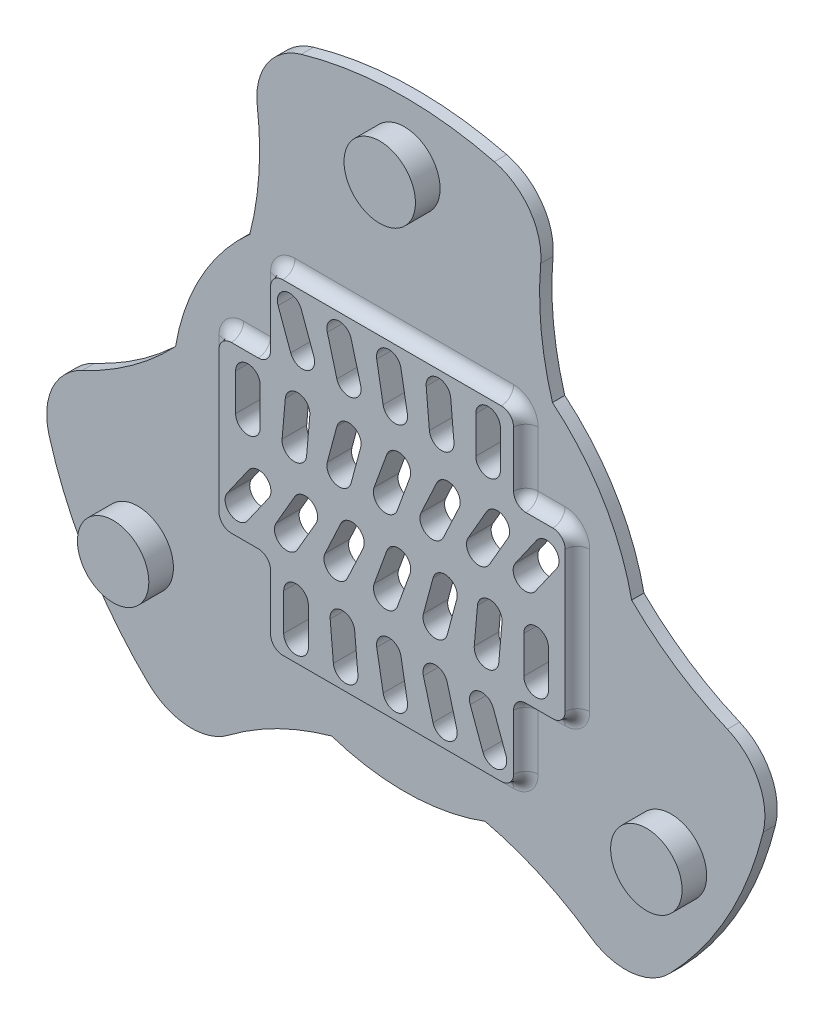
SolidWorks part; units mm, degrees
ref_plane "Спереди" through (0, 0, 0) normal (0, 0, 1) x (1, 0, 0)
ref_plane "Сверху" through (0, 0, 0) normal (0, 1, 0) x (1, 0, 0)
ref_plane "Справа" through (0, 0, 0) normal (1, 0, 0) x (0, 0, -1)
sketch "Sketch1" plane through (0, 0, 0) normal (0, 0, 1) x (1, 0, 0)
  line L0 (3.9, 6.755) -> (7.8, 0) construction
  line L2 (5.85, 10.1325) -> (11.7, 0) construction
  line L4 (7.8, 13.51) -> (15.6, 0) construction
  circle A61 centre (0, 0) radius 20
  circle A131 centre (0, 0) radius 1.25
  circle A484 centre (3.9, 0) radius 1.25
  circle A485 centre (7.8, 0) radius 1.25
  circle A486 centre (11.7, 0) radius 1.25
  circle A487 centre (15.6, 0) radius 1.25
  circle A488 centre (1.95, -3.3775) radius 1.25
  circle A489 centre (3.9, -6.755) radius 1.25
  circle A490 centre (5.85, -10.1325) radius 1.25
  circle A491 centre (7.8, -13.51) radius 1.25
  circle A492 centre (-1.95, -3.3775) radius 1.25
  circle A493 centre (-3.9, -6.755) radius 1.25
  circle A494 centre (-5.85, -10.1325) radius 1.25
  circle A495 centre (-7.8, -13.51) radius 1.25
  circle A496 centre (-3.9, 0) radius 1.25
  circle A497 centre (-7.8, 0) radius 1.25
  circle A498 centre (-11.7, 0) radius 1.25
  circle A499 centre (-15.6, 0) radius 1.25
  circle A500 centre (-1.95, 3.3775) radius 1.25
  circle A501 centre (-3.9, 6.755) radius 1.25
  circle A502 centre (-5.85, 10.1325) radius 1.25
  circle A503 centre (-7.8, 13.51) radius 1.25
  circle A504 centre (1.95, 3.3775) radius 1.25
  circle A505 centre (3.9, 6.755) radius 1.25
  circle A506 centre (5.85, 10.1325) radius 1.25
  circle A507 centre (7.8, 13.51) radius 1.25
  circle A508 centre (5.85, 3.3775) radius 1.25
  circle A509 centre (7.8, 6.755) radius 1.25
  circle A510 centre (9.75, 3.3775) radius 1.25
  circle A511 centre (11.7, 6.755) radius 1.25
  circle A512 centre (9.7491, 10.1341) radius 1.25
  circle A513 centre (13.6509, 3.3759) radius 1.25
  circle A514 centre (5.85, -3.3791) radius 1.25
  circle A515 centre (9.75, -3.3791) radius 1.25
  circle A516 centre (7.8, -6.7566) radius 1.25
  circle A517 centre (11.7, -6.7566) radius 1.25
  circle A518 centre (9.7491, -10.1356) radius 1.25
  circle A519 centre (13.6509, -3.3775) radius 1.25
  circle A520 centre (-0.0013, -6.7573) radius 1.25
  circle A521 centre (1.9487, -10.1348) radius 1.25
  circle A522 centre (-1.9513, -10.1348) radius 1.25
  circle A523 centre (-0.0013, -13.5123) radius 1.25
  circle A524 centre (-3.9032, -13.5123) radius 1.25
  circle A525 centre (3.9005, -13.5123) radius 1.25
  circle A526 centre (-5.8527, -3.3791) radius 1.25
  circle A527 centre (-7.8027, -6.7566) radius 1.25
  circle A528 centre (-9.7527, -3.3791) radius 1.25
  circle A529 centre (-11.7027, -6.7566) radius 1.25
  circle A530 centre (-13.6536, -3.3775) radius 1.25
  circle A531 centre (-9.7518, -10.1356) radius 1.25
  circle A532 centre (-5.8527, 3.3775) radius 1.25
  circle A533 centre (-9.7527, 3.3775) radius 1.25
  circle A534 centre (-7.8027, 6.755) radius 1.25
  circle A535 centre (-11.7027, 6.755) radius 1.25
  circle A536 centre (-9.7518, 10.1341) radius 1.25
  circle A537 centre (-13.6536, 3.3759) radius 1.25
  circle A538 centre (-0.0014, 6.7558) radius 1.25
  circle A539 centre (-1.9514, 10.1333) radius 1.25
  circle A540 centre (1.9486, 10.1333) radius 1.25
  circle A541 centre (-0.0014, 13.5108) radius 1.25
  circle A542 centre (3.9005, 13.5108) radius 1.25
  circle A543 centre (-3.9032, 13.5108) radius 1.25
  circle A544 centre (13.65, -1.1258) radius 2.2517 construction
  circle A545 centre (11.7009, -4.5044) radius 2.2522 construction
  circle A546 centre (9.75, -7.8834) radius 2.2522 construction
  circle A547 centre (7.7987, -11.2591) radius 2.2509 construction
  circle A548 centre (13.65, -1.1258) radius 0.65
  circle A549 centre (11.7009, -4.5044) radius 0.65
  circle A550 centre (9.75, -7.8834) radius 0.65
  circle A551 centre (7.7987, -11.2591) radius 0.65
  circle A552 centre (9.75, -1.1258) radius 0.65
  circle A553 centre (7.8009, -4.5044) radius 0.65
  circle A554 centre (5.85, -7.8834) radius 0.65
  circle A555 centre (3.8987, -11.2591) radius 0.65
  circle A556 centre (5.85, -1.1258) radius 0.65
  circle A557 centre (3.9009, -4.5044) radius 0.65
  circle A558 centre (1.95, -7.8834) radius 0.65
  circle A559 centre (-0.0013, -11.2591) radius 0.65
  circle A560 centre (1.95, -1.1258) radius 0.65
  circle A561 centre (0.0009, -4.5044) radius 0.65
  circle A562 centre (-1.95, -7.8834) radius 0.65
  circle A563 centre (-3.9013, -11.2591) radius 0.65
  circle A564 centre (-1.95, -1.1258) radius 0.65
  circle A565 centre (-3.8991, -4.5044) radius 0.65
  circle A566 centre (-5.85, -7.8834) radius 0.65
  circle A567 centre (-7.8013, -11.2591) radius 0.65
  circle A568 centre (-5.85, -1.1258) radius 0.65
  circle A569 centre (-7.7991, -4.5044) radius 0.65
  circle A570 centre (-9.75, -7.8834) radius 0.65
  circle A572 centre (-9.75, -1.1258) radius 0.65
  circle A573 centre (-11.6991, -4.5044) radius 0.65
  circle A576 centre (-13.65, -1.1258) radius 0.65
  circle A587 centre (0, 2.2517) radius 2.2517 construction
  circle A588 centre (0, 2.2517) radius 0.65
  circle A589 centre (3.9, 2.2517) radius 0.65
  circle A590 centre (7.8, 2.2517) radius 0.65
  circle A591 centre (11.7, 2.2517) radius 0.65
  circle A592 centre (15.6, 2.2517) radius 0.65
  circle A593 centre (1.9491, 5.6297) radius 2.2522 construction
  circle A594 centre (1.9491, 5.6297) radius 0.65
  circle A595 centre (5.8491, 5.6297) radius 0.65
  circle A596 centre (9.7491, 5.6297) radius 0.65
  circle A597 centre (13.6491, 5.6297) radius 0.65
  circle A598 centre (3.8991, 9.0072) radius 2.2522 construction
  circle A599 centre (3.8991, 9.0072) radius 0.65
  circle A600 centre (7.7991, 9.0072) radius 0.65
  circle A601 centre (11.6991, 9.0072) radius 0.65
  circle A602 centre (5.85, 12.3842) radius 2.2517 construction
  circle A603 centre (5.85, 12.3842) radius 0.65
  circle A604 centre (9.75, 12.3842) radius 0.65
  circle A605 centre (5.85, -14.6358) radius 0.65
  circle A606 centre (1.9509, -14.6353) radius 0.65
  circle A607 centre (-1.9491, -14.6353) radius 0.65
  circle A608 centre (-5.85, -14.6358) radius 0.65
  circle A609 centre (-15.6, 2.2517) radius 0.65
  circle A610 centre (-13.65, 5.6281) radius 0.65
  circle A611 centre (-11.7, 9.0056) radius 0.65
  circle A612 centre (-9.75, 12.3842) radius 0.65
  circle A613 centre (-5.85, 12.3842) radius 0.65
  circle A614 centre (-1.95, 12.3842) radius 0.65
  circle A615 centre (1.95, 12.3842) radius 0.65
  circle A616 centre (-7.8, 9.0056) radius 0.65
  circle A617 centre (-9.75, 5.6281) radius 0.65
  circle A618 centre (-11.7, 2.2517) radius 0.65
  circle A619 centre (-3.9, 9.0056) radius 0.65
  circle A620 centre (-5.85, 5.6281) radius 0.65
  circle A621 centre (-7.8, 2.2517) radius 0.65
  circle A622 centre (0, 9.0056) radius 0.65
  circle A623 centre (-1.95, 5.6281) radius 0.65
  circle A624 centre (-3.9, 2.2517) radius 0.65
  circle A625 centre (-15.5991, -4.5044) radius 0.65
  circle A626 centre (-13.65, -7.8834) radius 0.65
  circle A627 centre (-17.55, -7.8834) radius 0.65
  circle A628 centre (-19.5013, -11.2591) radius 0.65
  circle A629 centre (-15.6013, -11.2591) radius 0.65
  circle A630 centre (-11.7013, -11.2591) radius 0.65
  point P51 (0, 0)
  point P125 (-0.0013, -0.0008)
  point P231 (0, 0)
  dimension "D1" = 5
  dimension "D3" = 6
  dimension "D5" = 8
  dimension "D7" = 4
  dimension "D11" = 4
  dimension "D2" = 6
  dimension "D6" = 5
  dimension "D8" = 3
  dimension "D9" = 2
  dimension "D4" = 1.3
  dimension "D10" = 3
ref_plane "Plane1" through (0, 0, 10) normal (0, 0, 1) x (1, 0, 0)
sketch "Sketch2" plane through (0, 0, 10) normal (0, 0, 1) x (1, 0, 0)
  line L2 (8.0291, 21.9345) -> (-10.7971, 21.9345) construction
  circle A52 centre (0, 0) radius 16.85 construction
  circle A53 centre (0, 0) radius 18.85
  point P5 (0, 0)
  line B0 (4.7641, 11.7139) -> (5.0256, 8.7254)
  arc B1 (3.0332, 8.551) -> (5.0256, 8.7254) centre (4.0294, 8.6382) ccw
  line B2 (2.7717, 11.5396) -> (3.0332, 8.551)
  arc B3 (4.7641, 11.7139) -> (2.7717, 11.5396) centre (3.7679, 11.6268) ccw
  line B4 (3.7679, 11.6268) -> (4.0294, 8.6382) construction
  line B5 (0.722, 11.7838) -> (1.2429, 8.8293)
  arc B6 (-0.7267, 8.482) -> (1.2429, 8.8293) centre (0.2581, 8.6557) ccw
  line B7 (-1.2476, 11.4365) -> (-0.7267, 8.482)
  arc B8 (0.722, 11.7838) -> (-1.2476, 11.4365) centre (-0.2628, 11.6101) ccw
  line B9 (-0.2628, 11.6101) -> (0.2581, 8.6557) construction
  line B10 (-3.3247, 11.8406) -> (-2.5482, 8.9428)
  arc B11 (-4.48, 8.4252) -> (-2.5482, 8.9428) centre (-3.5141, 8.684) ccw
  line B12 (-5.2565, 11.323) -> (-4.48, 8.4252)
  arc B13 (-3.3247, 11.8406) -> (-5.2565, 11.323) centre (-4.2906, 11.5818) ccw
  line B14 (-4.2906, 11.5818) -> (-3.5141, 8.684) construction
  line B15 (-7.3747, 11.8841) -> (-6.3486, 9.065)
  arc B16 (-8.228, 8.3809) -> (-6.3486, 9.065) centre (-7.2883, 8.723) ccw
  line B17 (-9.2541, 11.2) -> (-8.228, 8.3809)
  arc B18 (-7.3747, 11.8841) -> (-9.2541, 11.2) centre (-8.3144, 11.542) ccw
  line B19 (-8.3144, 11.542) -> (-7.2883, 8.723) construction
  line B20 (10.0165, 2.7228) -> (11.7373, 5.1803)
  arc B21 (13.3756, 4.0332) -> (11.7373, 5.1803) centre (12.5564, 4.6067) ccw
  line B22 (11.6548, 1.5757) -> (13.3756, 4.0332)
  arc B23 (10.0165, 2.7228) -> (11.6548, 1.5757) centre (10.8357, 2.1493) ccw
  line B24 (10.8357, 2.1493) -> (12.5564, 4.6067) construction
  line B25 (6.18, 2.579) -> (7.68, 5.177)
  arc B26 (9.4121, 4.177) -> (7.68, 5.177) centre (8.546, 4.677) ccw
  line B27 (7.9121, 1.579) -> (9.4121, 4.177)
  arc B28 (6.18, 2.579) -> (7.9121, 1.579) centre (7.046, 2.079) ccw
  line B29 (7.046, 2.079) -> (8.546, 4.677) construction
  line B30 (2.3558, 2.4412) -> (3.6237, 5.1601)
  arc B31 (5.4363, 4.3148) -> (3.6237, 5.1601) centre (4.53, 4.7375) ccw
  line B32 (4.1684, 1.5959) -> (5.4363, 4.3148)
  arc B33 (2.3558, 2.4412) -> (4.1684, 1.5959) centre (3.2621, 2.0185) ccw
  line B34 (3.2621, 2.0185) -> (4.53, 4.7375) construction
  line B35 (-1.4567, 2.3105) -> (-0.4306, 5.1296)
  arc B36 (1.4488, 4.4455) -> (-0.4306, 5.1296) centre (0.5091, 4.7875) ccw
  line B37 (0.4227, 1.6264) -> (1.4488, 4.4455)
  arc B38 (-1.4567, 2.3105) -> (0.4227, 1.6264) centre (-0.517, 1.9685) ccw
  line B39 (-0.517, 1.9685) -> (0.5091, 4.7875) construction
  line B40 (-5.2581, 2.1879) -> (-4.4816, 5.0857)
  arc B41 (-2.5498, 4.5681) -> (-4.4816, 5.0857) centre (-3.5157, 4.8269) ccw
  line B42 (-3.3263, 1.6703) -> (-2.5498, 4.5681)
  arc B43 (-5.2581, 2.1879) -> (-3.3263, 1.6703) centre (-4.2922, 1.9291) ccw
  line B44 (-4.2922, 1.9291) -> (-3.5157, 4.8269) construction
  line B45 (-8.9296, 1.9704) -> (-8.6682, 4.9589)
  arc B46 (-6.6758, 4.7846) -> (-8.6682, 4.9589) centre (-7.672, 4.8718) ccw
  line B47 (-6.9372, 1.7961) -> (-6.6758, 4.7846)
  arc B48 (-8.9296, 1.9704) -> (-6.9372, 1.7961) centre (-7.9334, 1.8832) ccw
  line B49 (-7.9334, 1.8832) -> (-7.672, 4.8718) construction
  line B50 (-12.704, 1.878) -> (-12.704, 4.878)
  arc B51 (-10.704, 4.878) -> (-12.704, 4.878) centre (-11.704, 4.878) ccw
  line B52 (-10.704, 1.878) -> (-10.704, 4.878)
  arc B53 (-12.704, 1.878) -> (-10.704, 1.878) centre (-11.704, 1.878) ccw
  line B54 (-11.704, 1.878) -> (-11.704, 4.878) construction
  line B55 (8.7976, 11.6329) -> (8.7976, 8.6329)
  arc B56 (6.7976, 8.6329) -> (8.7976, 8.6329) centre (7.7976, 8.6329) ccw
  line B57 (6.7976, 11.6329) -> (6.7976, 8.6329)
  arc B58 (8.7976, 11.6329) -> (6.7976, 11.6329) centre (7.7976, 11.6329) ccw
  line B59 (-4.7641, -11.7139) -> (-5.0256, -8.7254)
  arc B60 (-3.0332, -8.551) -> (-5.0256, -8.7254) centre (-4.0294, -8.6382) ccw
  line B61 (-2.7717, -11.5396) -> (-3.0332, -8.551)
  arc B62 (-4.7641, -11.7139) -> (-2.7717, -11.5396) centre (-3.7679, -11.6268) ccw
  line B63 (-0.722, -11.7838) -> (-1.2429, -8.8293)
  arc B64 (0.7267, -8.482) -> (-1.2429, -8.8293) centre (-0.2581, -8.6557) ccw
  line B65 (1.2476, -11.4365) -> (0.7267, -8.482)
  arc B66 (-0.722, -11.7838) -> (1.2476, -11.4365) centre (0.2628, -11.6101) ccw
  line B67 (3.3247, -11.8406) -> (2.5482, -8.9428)
  arc B68 (4.48, -8.4252) -> (2.5482, -8.9428) centre (3.5141, -8.684) ccw
  line B69 (5.2565, -11.323) -> (4.48, -8.4252)
  arc B70 (3.3247, -11.8406) -> (5.2565, -11.323) centre (4.2906, -11.5818) ccw
  line B71 (7.3747, -11.8841) -> (6.3486, -9.065)
  arc B72 (8.228, -8.3809) -> (6.3486, -9.065) centre (7.2883, -8.723) ccw
  line B73 (9.2541, -11.2) -> (8.228, -8.3809)
  arc B74 (7.3747, -11.8841) -> (9.2541, -11.2) centre (8.3144, -11.542) ccw
  line B75 (-10.0165, -2.7228) -> (-11.7373, -5.1803)
  arc B76 (-13.3756, -4.0332) -> (-11.7373, -5.1803) centre (-12.5564, -4.6067) ccw
  line B77 (-11.6548, -1.5757) -> (-13.3756, -4.0332)
  arc B78 (-10.0165, -2.7228) -> (-11.6548, -1.5757) centre (-10.8357, -2.1493) ccw
  line B79 (-6.18, -2.579) -> (-7.68, -5.177)
  arc B80 (-9.4121, -4.177) -> (-7.68, -5.177) centre (-8.546, -4.677) ccw
  line B81 (-7.9121, -1.579) -> (-9.4121, -4.177)
  arc B82 (-6.18, -2.579) -> (-7.9121, -1.579) centre (-7.046, -2.079) ccw
  line B83 (-2.3558, -2.4412) -> (-3.6237, -5.1601)
  arc B84 (-5.4363, -4.3148) -> (-3.6237, -5.1601) centre (-4.53, -4.7375) ccw
  line B85 (-4.1684, -1.5959) -> (-5.4363, -4.3148)
  arc B86 (-2.3558, -2.4412) -> (-4.1684, -1.5959) centre (-3.2621, -2.0185) ccw
  line B87 (1.4567, -2.3105) -> (0.4306, -5.1296)
  arc B88 (-1.4488, -4.4455) -> (0.4306, -5.1296) centre (-0.5091, -4.7875) ccw
  line B89 (-0.4227, -1.6264) -> (-1.4488, -4.4455)
  arc B90 (1.4567, -2.3105) -> (-0.4227, -1.6264) centre (0.517, -1.9685) ccw
  line B91 (5.2581, -2.1879) -> (4.4816, -5.0857)
  arc B92 (2.5498, -4.5681) -> (4.4816, -5.0857) centre (3.5157, -4.8269) ccw
  line B93 (3.3263, -1.6703) -> (2.5498, -4.5681)
  arc B94 (5.2581, -2.1879) -> (3.3263, -1.6703) centre (4.2922, -1.9291) ccw
  line B95 (8.9296, -1.9704) -> (8.6682, -4.9589)
  arc B96 (6.6758, -4.7846) -> (8.6682, -4.9589) centre (7.672, -4.8718) ccw
  line B97 (6.9372, -1.7961) -> (6.6758, -4.7846)
  arc B98 (8.9296, -1.9704) -> (6.9372, -1.7961) centre (7.9334, -1.8832) ccw
  line B99 (12.704, -1.878) -> (12.704, -4.878)
  arc B100 (10.704, -4.878) -> (12.704, -4.878) centre (11.704, -4.878) ccw
  line B101 (10.704, -1.878) -> (10.704, -4.878)
  arc B102 (12.704, -1.878) -> (10.704, -1.878) centre (11.704, -1.878) ccw
  line B103 (-8.7976, -11.6329) -> (-8.7976, -8.6329)
  arc B104 (-6.7976, -8.6329) -> (-8.7976, -8.6329) centre (-7.7976, -8.6329) ccw
  line B105 (-6.7976, -11.6329) -> (-6.7976, -8.6329)
  arc B106 (-8.7976, -11.6329) -> (-6.7976, -11.6329) centre (-7.7976, -11.6329) ccw
  dimension "D15" = 2
  dimension "D2" = 95
  dimension "D4" = 105
  dimension "D5" = 110
  dimension "D6" = 55
  dimension "D7" = 60
  dimension "D9" = 70
  dimension "D12" = 90
  dimension "D13" = 2
  dimension "D3" = 100
  dimension "D8" = 65
  dimension "D10" = 75
  dimension "D11" = 85
sketch_block_instance "Block4-1"
sketch_block "Block4"
sketch_block_instance "Block5-1"
sketch_block "Block5"
sketch_block_instance "Block6-1"
sketch_block "Block6"
sketch_block_instance "Block7-1"
sketch_block "Block7" parameters "D1"=2, "D2"=3
sketch_block_instance "Block8-1"
sketch_block "Block8"
sketch_block_instance "Block9-1"
sketch_block "Block9"
sketch_block_instance "Block10-1"
sketch_block "Block10"
sketch_block_instance "Block11-1"
sketch_block "Block11"
sketch_block_instance "Block12-1"
sketch_block "Block12"
sketch_block_instance "Block13-1"
sketch_block "Block13" parameters "D1"=2, "D2"=3
sketch_block_instance "Block14-1"
sketch_block "Block14"
sketch_block_instance "Block28-1"
sketch_block "Block28"
sketch_block_instance "Block4-2"
sketch_block_instance "Block5-2"
sketch_block_instance "Block6-2"
sketch_block_instance "Block7-2"
sketch_block_instance "Block8-2"
sketch_block_instance "Block9-2"
sketch_block_instance "Block10-2"
sketch_block_instance "Block11-2"
sketch_block_instance "Block12-2"
sketch_block_instance "Block13-2"
sketch_block_instance "Block14-2"
sketch_block_instance "Block28-2"
extrude "Boss-Extrude1" add sketch "Sketch2" along normal blind 8
sketch "Sketch3" plane through (0, 0, 18) normal (0, 0, 1) x (1, 0, 0)
  circle A0 centre (0, 0) radius 17.6
  circle A1 centre (0, 0) radius 30
extrude "Boss-Extrude2" add sketch "Sketch3" against normal up to surface (8 mm away) up to face at (11.704, -3.378, 10)
sketch "Sketch4" plane through (0, 0, 18) normal (0, 0, 1) x (1, 0, 0)
  circle A0 centre (0, 0) radius 25 construction
  circle A1 centre (0, 25) radius 2.9
  circle A2 centre (21.6506, -12.5) radius 2.9
  circle A3 centre (-21.6506, -12.5) radius 2.9
  point P11 (0, 0)
  dimension "D1" = 3
extrude "Boss-Extrude3" add sketch "Sketch4" along normal blind 2
sketch "Sketch6" plane through (0, 0, 10) normal (0, 0, -1) x (-1, 0, 0)
  circle A0 centre (0, 30) radius 5
  circle A1 centre (0, 0) radius 30 construction
  circle A2 centre (25.9808, -15) radius 5
  circle A3 centre (-25.9808, -15) radius 5
  point P10 (0, 0)
  dimension "D1" = 3
extrude "Boss-Extrude4" add sketch "Sketch6" against normal blind 3
sketch "Sketch5" plane through (0, 0, 10) normal (0, 0, -1) x (-1, 0, 0)
  circle A0 centre (0, 25) radius 3
  circle A1 centre (21.6506, -12.5) radius 3
  circle A2 centre (-21.6506, -12.5) radius 3
extrude "Cut-Extrude1" cut sketch "Sketch5" against normal blind 3
sketch "Sketch7" plane through (0, 0, 10) normal (0, 0, -1) x (-1, 0, 0)
  line L0 (0, 0) -> (-35.9801, 21.6664) construction
  circle A0 centre (0, 0) radius 42 construction
  circle A1 centre (-35.9801, 21.6664) radius 25
  circle A2 centre (36.7537, 20.3265) radius 25
  circle A3 centre (-0.7736, -41.9929) radius 25
  point P11 (0, 0)
  dimension "D1" = 3
extrude "Cut-Extrude2" cut sketch "Sketch7" against normal blind 8
fillet "Fillet1" radius 5 6 edges at (-12.7099, 27.1746, 14) (-29.7735, -3.6793, 14) (-17.1789, -24.5944, 14) (18.0731, -23.945, 14) (29.8888, -2.5802, 14) (11.7004, 27.6243, 14)
sketch "Sketch8"
sketch_block_instance "Block1-1"
sketch_block "Block1" parameters "D1"=2, "D2"=3
sketch_block_instance "Block3-1"
sketch_block "Block3" parameters "D1"=2, "D2"=3
sketch "Sketch9" plane through (0, 0, 0) normal (0, 0, 1) x (1, 0, 0)
  line L0 (-7.8, 13.51) -> (-7.8027, 6.755) construction
  line L1 (-9.7518, 10.1341) -> (-5.85, 10.1325) construction
  line L2 (-7.8008, 11.6325) -> (-7.8019, 8.6325) construction
  line L3 (-6.8008, 11.6321) -> (-6.8019, 8.6321)
  line L4 (-8.8008, 11.6329) -> (-8.8019, 8.6329)
  line L5 (-4.9008, 11.6329) -> (-4.9019, 8.6329)
  line L6 (-2.9008, 11.6321) -> (-2.9019, 8.6321)
  line L7 (-3.9008, 11.6325) -> (-3.9019, 8.6325) construction
  line L8 (-1.0008, 11.6329) -> (-1.0019, 8.6329)
  line L9 (0.9992, 11.6321) -> (0.9981, 8.6321)
  line L10 (-0.0008, 11.6325) -> (-0.0019, 8.6325) construction
  line L11 (2.8992, 11.6329) -> (2.8981, 8.6329)
  line L12 (4.8992, 11.6321) -> (4.8981, 8.6321)
  line L13 (3.8992, 11.6325) -> (3.8981, 8.6325) construction
  line L14 (6.7992, 11.6329) -> (6.7981, 8.6329)
  line L15 (8.7992, 11.6321) -> (8.7981, 8.6321)
  line L16 (7.7992, 11.6325) -> (7.7981, 8.6325) construction
  line L17 (-9.7518, 10.1341) -> (-9.7527, 3.3775) construction
  line L18 (-11.7027, 6.755) -> (-7.8027, 6.755) construction
  line L19 (-10.7035, 1.877) -> (-10.702, 4.877)
  line L22 (-9.7527, 3.3775) -> (-5.8527, 3.3775) construction
  line L25 (-7.8027, 6.755) -> (-7.8, 0) construction
  line L26 (-7.8035, 1.8775) -> (-7.8019, 4.8775) construction
  line L27 (-8.8035, 1.878) -> (-8.8019, 4.878)
  line L28 (-6.8035, 1.877) -> (-6.8019, 4.877)
  line L29 (-2.9035, 1.877) -> (-2.9019, 4.877)
  line L30 (-4.9035, 1.878) -> (-4.9019, 4.878)
  line L31 (-3.9035, 1.8775) -> (-3.9019, 4.8775) construction
  line L32 (0.9965, 1.877) -> (0.9981, 4.877)
  line L33 (-1.0035, 1.878) -> (-1.0019, 4.878)
  line L34 (-0.0035, 1.8775) -> (-0.0019, 4.8775) construction
  line L35 (4.8965, 1.877) -> (4.8981, 4.877)
  line L36 (2.8965, 1.878) -> (2.8981, 4.878)
  line L37 (3.8965, 1.8775) -> (3.8981, 4.8775) construction
  line L38 (8.7965, 1.877) -> (8.7981, 4.877)
  line L39 (6.7965, 1.878) -> (6.7981, 4.878)
  line L40 (7.7965, 1.8775) -> (7.7981, 4.8775) construction
  line L41 (12.6965, 1.877) -> (12.6981, 4.877)
  line L42 (10.6965, 1.878) -> (10.6981, 4.878)
  line L43 (11.6965, 1.8775) -> (11.6981, 4.8775) construction
  line L44 (-12.7035, 1.878) -> (-12.7019, 4.878)
  line L45 (-11.7035, 1.8775) -> (-11.702, 4.8775) construction
  line L46 (-9.7527, -3.3791) -> (-5.8527, -3.3791) construction
  line L47 (-7.8, 0) -> (-7.8027, -6.7566) construction
  line L48 (-7.8046, -4.8791) -> (-7.8008, -1.8791) construction
  line L49 (-8.8046, -4.8778) -> (-8.8008, -1.8778)
  line L50 (-6.8046, -4.8804) -> (-6.8008, -1.8804)
  line L51 (-2.9046, -4.8804) -> (-2.9008, -1.8804)
  line L52 (-4.9046, -4.8778) -> (-4.9008, -1.8778)
  line L53 (-3.9046, -4.8791) -> (-3.9008, -1.8791) construction
  line L54 (0.9954, -4.8804) -> (0.9992, -1.8804)
  line L55 (-1.0046, -4.8778) -> (-1.0008, -1.8778)
  line L56 (-0.0046, -4.8791) -> (-0.0008, -1.8791) construction
  line L57 (4.8954, -4.8804) -> (4.8992, -1.8804)
  line L58 (2.8954, -4.8778) -> (2.8992, -1.8778)
  line L59 (3.8954, -4.8791) -> (3.8992, -1.8791) construction
  line L60 (8.7954, -4.8804) -> (8.7992, -1.8804)
  line L61 (6.7954, -4.8778) -> (6.7992, -1.8778)
  line L62 (7.7954, -4.8791) -> (7.7992, -1.8791) construction
  line L63 (12.6954, -4.8804) -> (12.6992, -1.8804)
  line L64 (10.6954, -4.8778) -> (10.6992, -1.8778)
  line L65 (11.6954, -4.8791) -> (11.6992, -1.8791) construction
  line L66 (-10.7046, -4.8804) -> (-10.7008, -1.8804)
  line L67 (-12.7046, -4.8778) -> (-12.7008, -1.8778)
  line L68 (-11.7046, -4.8791) -> (-11.7008, -1.8791) construction
  line L69 (-9.7518, -10.1356) -> (-5.482, -10.1356) construction
  line L70 (-7.8027, -6.7566) -> (-7.8, -13.51) construction
  line L71 (-7.8007, -8.6356) -> (-7.8007, -11.6356) construction
  line L72 (-6.8007, -8.6356) -> (-6.8007, -11.6356)
  line L73 (-8.8007, -8.6356) -> (-8.8007, -11.6356)
  line L74 (-4.9007, -8.6356) -> (-4.9007, -11.6356)
  line L75 (-2.9007, -8.6356) -> (-2.9007, -11.6356)
  line L76 (-3.9007, -8.6356) -> (-3.9007, -11.6356) construction
  line L77 (-1.0007, -8.6356) -> (-1.0007, -11.6356)
  line L78 (0.9993, -8.6356) -> (0.9993, -11.6356)
  line L79 (-0.0007, -8.6356) -> (-0.0007, -11.6356) construction
  line L80 (2.8993, -8.6356) -> (2.8993, -11.6356)
  line L81 (4.8993, -8.6356) -> (4.8993, -11.6356)
  line L82 (3.8993, -8.6356) -> (3.8993, -11.6356) construction
  line L83 (6.7993, -8.6356) -> (6.7993, -11.6356)
  line L84 (8.7993, -8.6356) -> (8.7993, -11.6356)
  line L85 (7.7993, -8.6356) -> (7.7993, -11.6356) construction
  arc A0 (-6.8008, 11.6321) -> (-8.8008, 11.6329) centre (-7.8008, 11.6325) ccw
  arc A1 (-8.8019, 8.6329) -> (-6.8019, 8.6321) centre (-7.8019, 8.6325) ccw
  arc A2 (-2.9008, 11.6321) -> (-4.9008, 11.6329) centre (-3.9008, 11.6325) ccw
  arc A3 (-4.9019, 8.6329) -> (-2.9019, 8.6321) centre (-3.9019, 8.6325) ccw
  arc A4 (0.9992, 11.6321) -> (-1.0008, 11.6329) centre (-0.0008, 11.6325) ccw
  arc A5 (-1.0019, 8.6329) -> (0.9981, 8.6321) centre (-0.0019, 8.6325) ccw
  arc A6 (4.8992, 11.6321) -> (2.8992, 11.6329) centre (3.8992, 11.6325) ccw
  arc A7 (2.8981, 8.6329) -> (4.8981, 8.6321) centre (3.8981, 8.6325) ccw
  arc A8 (8.7992, 11.6321) -> (6.7992, 11.6329) centre (7.7992, 11.6325) ccw
  arc A9 (6.7981, 8.6329) -> (8.7981, 8.6321) centre (7.7981, 8.6325) ccw
  arc A14 (-8.8035, 1.878) -> (-6.8035, 1.877) centre (-7.8035, 1.8775) ccw
  arc A15 (-6.8019, 4.877) -> (-8.8019, 4.878) centre (-7.8019, 4.8775) ccw
  arc A16 (-4.9035, 1.878) -> (-2.9035, 1.877) centre (-3.9035, 1.8775) ccw
  arc A17 (-2.9019, 4.877) -> (-4.9019, 4.878) centre (-3.9019, 4.8775) ccw
  arc A18 (-1.0035, 1.878) -> (0.9965, 1.877) centre (-0.0035, 1.8775) ccw
  arc A19 (0.9981, 4.877) -> (-1.0019, 4.878) centre (-0.0019, 4.8775) ccw
  arc A20 (2.8965, 1.878) -> (4.8965, 1.877) centre (3.8965, 1.8775) ccw
  arc A21 (4.8981, 4.877) -> (2.8981, 4.878) centre (3.8981, 4.8775) ccw
  arc A22 (6.7965, 1.878) -> (8.7965, 1.877) centre (7.7965, 1.8775) ccw
  arc A23 (8.7981, 4.877) -> (6.7981, 4.878) centre (7.7981, 4.8775) ccw
  arc A24 (10.6965, 1.878) -> (12.6965, 1.877) centre (11.6965, 1.8775) ccw
  arc A25 (12.6981, 4.877) -> (10.6981, 4.878) centre (11.6981, 4.8775) ccw
  arc A26 (-12.7035, 1.878) -> (-10.7035, 1.877) centre (-11.7035, 1.8775) ccw
  arc A27 (-10.702, 4.877) -> (-12.7019, 4.878) centre (-11.702, 4.8775) ccw
  arc A28 (-8.8046, -4.8778) -> (-6.8046, -4.8804) centre (-7.8046, -4.8791) ccw
  arc A29 (-6.8008, -1.8804) -> (-8.8008, -1.8778) centre (-7.8008, -1.8791) ccw
  arc A30 (-4.9046, -4.8778) -> (-2.9046, -4.8804) centre (-3.9046, -4.8791) ccw
  arc A31 (-2.9008, -1.8804) -> (-4.9008, -1.8778) centre (-3.9008, -1.8791) ccw
  arc A32 (-1.0046, -4.8778) -> (0.9954, -4.8804) centre (-0.0046, -4.8791) ccw
  arc A33 (0.9992, -1.8804) -> (-1.0008, -1.8778) centre (-0.0008, -1.8791) ccw
  arc A34 (2.8954, -4.8778) -> (4.8954, -4.8804) centre (3.8954, -4.8791) ccw
  arc A35 (4.8992, -1.8804) -> (2.8992, -1.8778) centre (3.8992, -1.8791) ccw
  arc A36 (6.7954, -4.8778) -> (8.7954, -4.8804) centre (7.7954, -4.8791) ccw
  arc A37 (8.7992, -1.8804) -> (6.7992, -1.8778) centre (7.7992, -1.8791) ccw
  arc A38 (10.6954, -4.8778) -> (12.6954, -4.8804) centre (11.6954, -4.8791) ccw
  arc A39 (12.6992, -1.8804) -> (10.6992, -1.8778) centre (11.6992, -1.8791) ccw
  arc A40 (-12.7046, -4.8778) -> (-10.7046, -4.8804) centre (-11.7046, -4.8791) ccw
  arc A41 (-10.7008, -1.8804) -> (-12.7008, -1.8778) centre (-11.7008, -1.8791) ccw
  arc A42 (-6.8007, -8.6356) -> (-8.8007, -8.6356) centre (-7.8007, -8.6356) ccw
  arc A43 (-8.8007, -11.6356) -> (-6.8007, -11.6356) centre (-7.8007, -11.6356) ccw
  arc A44 (-2.9007, -8.6356) -> (-4.9007, -8.6356) centre (-3.9007, -8.6356) ccw
  arc A45 (-4.9007, -11.6356) -> (-2.9007, -11.6356) centre (-3.9007, -11.6356) ccw
  arc A46 (0.9993, -8.6356) -> (-1.0007, -8.6356) centre (-0.0007, -8.6356) ccw
  arc A47 (-1.0007, -11.6356) -> (0.9993, -11.6356) centre (-0.0007, -11.6356) ccw
  arc A48 (4.8993, -8.6356) -> (2.8993, -8.6356) centre (3.8993, -8.6356) ccw
  arc A49 (2.8993, -11.6356) -> (4.8993, -11.6356) centre (3.8993, -11.6356) ccw
  arc A50 (8.7993, -8.6356) -> (6.7993, -8.6356) centre (7.7993, -8.6356) ccw
  arc A51 (6.7993, -11.6356) -> (8.7993, -11.6356) centre (7.7993, -11.6356) ccw
  circle A52 centre (0, 0) radius 16.85 construction
  circle A53 centre (0, 0) radius 18.85
  point P10 (-7.8014, 10.1325)
  point P18 (-3.9014, 10.1325)
  point P25 (-0.0014, 10.1325)
  point P32 (3.8986, 10.1325)
  point P39 (7.7986, 10.1325)
  point P50 (-11.7027, 3.3775)
  point P58 (-7.8027, 3.3775)
  point P68 (-3.9027, 3.3775)
  point P75 (-0.0027, 3.3775)
  point P82 (3.8973, 3.3775)
  point P89 (7.7973, 3.3775)
  point P96 (11.6973, 3.3775)
  point P108 (-7.8027, -3.3791)
  point P116 (-3.9027, -3.3791)
  point P123 (-0.0027, -3.3791)
  point P130 (3.8973, -3.3791)
  point P137 (7.7973, -3.3791)
  point P144 (11.6973, -3.3791)
  point P151 (-11.7027, -3.3791)
  point P162 (-7.8007, -10.1356)
  point P170 (-3.9007, -10.1356)
  point P177 (-0.0007, -10.1356)
  point P184 (3.8993, -10.1356)
  point P191 (7.7993, -10.1356)
  dimension "D1" = 2
  dimension "D15" = 2
  dimension "D2" = 3
  dimension "D4" = 2
  dimension "D5" = 3
  dimension "D6" = 2
  dimension "D7" = 3
  dimension "D9" = 2
  dimension "D12" = 3
  dimension "D13" = 2
  dimension "D3" = 5
  dimension "D8" = 6
  dimension "D10" = 6
  dimension "D11" = 2
  dimension "D14" = 5
extrude "Boss-Extrude5" add sketch "Sketch2<2>" along normal blind 10
sketch "Sketch2<2>" plane through (0, 0, 10) normal (0, 0, 1) x (1, 0, 0) same geometry as "Sketch2"
sketch "Sketch10" plane through (0, 0, 20) normal (0, 0, 1) x (1, 0, 0)
  line L1 (-9.8683, 13.2069) -> (9.8683, 13.2069)
  line L2 (-9.8683, 13.2069) -> (-9.8683, -13.2069)
  line L3 (-9.8683, -13.2069) -> (9.8683, -13.2069)
  line L4 (9.8683, 13.2069) -> (9.8683, -13.2069)
  line L5 (-9.8683, 13.2069) -> (9.8683, -13.2069) construction
  line L6 (-9.8683, -13.2069) -> (9.8683, 13.2069) construction
  line L7 (-14.0535, 6.7065) -> (14.0535, 6.7065)
  line L8 (-14.0535, 6.7065) -> (-14.0535, -6.7065)
  line L9 (-14.0535, -6.7065) -> (14.0535, -6.7065)
  line L10 (14.0535, 6.7065) -> (14.0535, -6.7065)
  line L11 (-14.0535, 6.7065) -> (14.0535, -6.7065) construction
  line L12 (-14.0535, -6.7065) -> (14.0535, 6.7065) construction
  circle A0 centre (0, 0) radius 21.6778
  point P0 (0, 0)
  point P6 (0, 0)
extrude "Cut-Extrude3" cut sketch "Sketch10" against normal blind 2 contours A0 L7 L10 L9 L4 L3 L2 L8 L1 region at (-21.0647, 0, 20)
fillet "Fillet2" radius 1 23 edges at (-11.9609, -6.7065, 18) (0, -13.2069, 18) (-14.0535, 0, 18) (-9.8683, 9.9567, 18) (11.9609, -6.7065, 18) (9.8683, -6.7065, 19) (9.8683, -13.2069, 19) (9.8683, -9.9567, 18) (-9.8683, -9.9567, 18) (-9.8683, -13.2069, 19) (-9.8683, -6.7065, 19) (-14.0535, -6.7065, 19) (-11.9609, 6.7065, 18) (-14.0535, 6.7065, 19) (-9.8683, 6.7065, 19) (-9.8683, 13.2069, 19) (9.8683, 13.2069, 19) (14.0535, 6.7065, 19) (14.0535, -6.7065, 19) (14.0535, 0, 18) (11.9609, 6.7065, 18) (9.8683, 9.9567, 18) (0, 13.2069, 18)
fillet "Fillet3" radius 1 2 edges at (10.1612, 6.9994, 18.2929) (9.8683, 6.7065, 19.5)
sketch "Sketch11" plane through (0, 0, 10) normal (0, 0, -1) x (-1, 0, 0)
  circle A0 centre (0, 0) radius 37.1303
extrude "Cut-Extrude4" cut sketch "Sketch11" against normal blind 7
sketch "Sketch12" plane through (0, 0, 20) normal (0, 0, 1) x (1, 0, 0)
  circle A0 centre (0, 0) radius 19.1771
extrude "Cut-Extrude5" cut sketch "Sketch12" against normal blind 1
